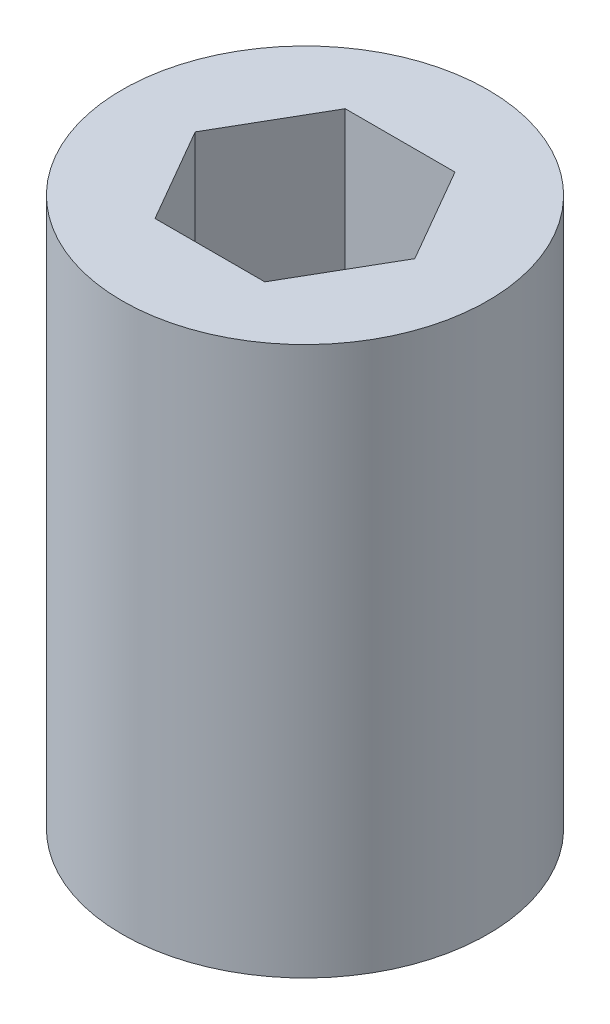
SolidWorks part; units mm, degrees
ref_plane "Front Plane" through (0, 0, 0) normal (0, 0, 1) x (1, 0, 0)
ref_plane "Top Plane" through (0, 0, 0) normal (0, 1, 0) x (1, 0, 0)
ref_plane "Right Plane" through (0, 0, 0) normal (1, 0, 0) x (0, 0, -1)
sketch "Sketch1" plane through (0, 0, 0) normal (0, 1, 0) x (1, 0, 0)
  circle A0 centre (0, 0) radius 12.7
  dimension "D1" = 25.4
extrude "Boss-Extrude1" add sketch "Sketch1" along normal blind 38.1
sketch "Sketch2" plane through (0, 38.1, 0) normal (0, 1, 0) x (1, 0, 0)
  circle A0 centre (0, 0) radius 12.7
extrude "Boss-Extrude2" [suppressed] add sketch "Sketch2" against normal blind 50.8 draft 5 draft outward yes
sketch "Sketch3" plane through (0, 0, 0) normal (0, -1, 0) x (-1, 0, 0)
  circle A0 centre (0, 0) radius 12.7
extrude "Boss-Extrude3" [suppressed] add sketch "Sketch3" against normal blind 50.8 draft 5 draft outward yes
sketch "Sketch5" plane through (0, 0, 0) normal (0, -1, 0) x (-1, 0, 0)
  line L1 (-7.6256, 0) -> (-3.8128, -6.604)
  line L2 (-3.8128, -6.604) -> (3.8128, -6.604)
  line L3 (3.8128, -6.604) -> (7.6256, 0)
  line L4 (7.6256, 0) -> (3.8128, 6.604)
  line L5 (3.8128, 6.604) -> (-3.8128, 6.604)
  line L6 (-3.8128, 6.604) -> (-7.6256, 0)
  circle A0 centre (0, 0) radius 6.604 construction
  dimension "D1" = 13.208
extrude "Cut-Extrude1" cut sketch "Sketch5" against normal through all
